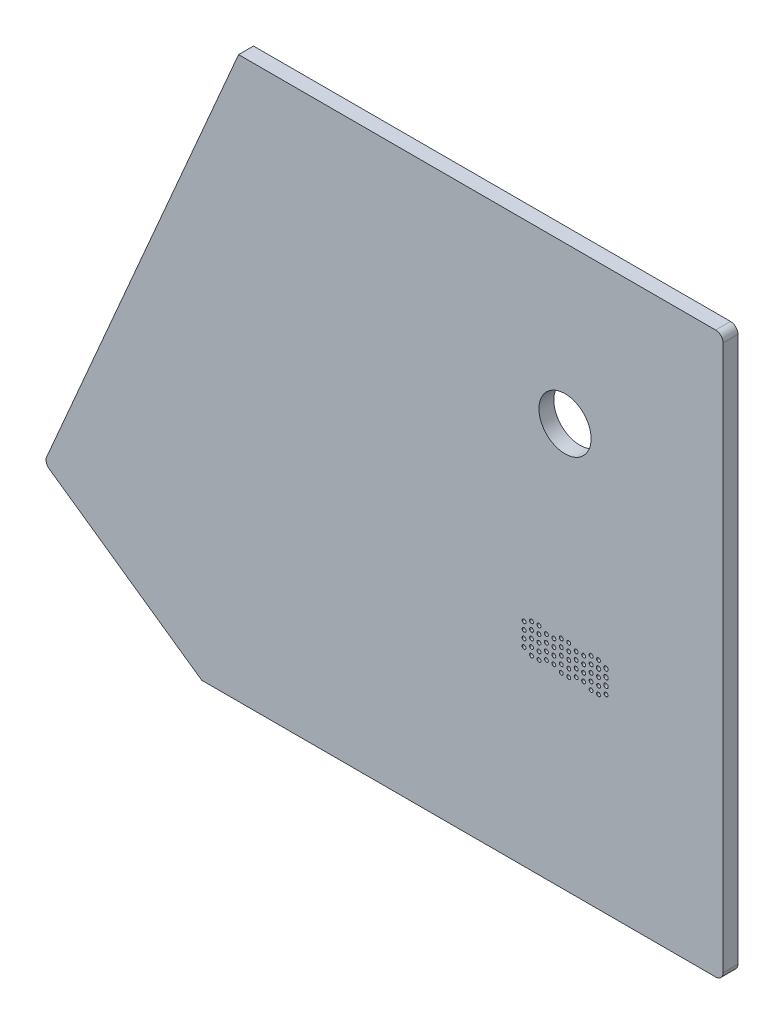
SolidWorks part; units mm, degrees
ref_plane "Plano frontal" through (0, 0, 0) normal (0, 0, 1) x (1, 0, 0)
ref_plane "Plano superior" through (0, 0, 0) normal (0, 1, 0) x (1, 0, 0)
ref_plane "Plano direito" through (0, 0, 0) normal (1, 0, 0) x (0, 0, -1)
sketch "Esboço1" plane through (0, 0, 0) normal (0, 0, 1) x (1, 0, 0)
  line L0 (0, 0) -> (138, 0)
  line L1 (140, 2) -> (140, 148.4543)
  line L2 (138, 150.4543) -> (9.8994, 150.4543)
  line L3 (9.8994, 150.4543) -> (-41.6465, 31.1101)
  line L4 (-40.9576, 28.6788) -> (0, 0)
  line L5 (0, 0) -> (-36.2791, 0) construction
  arc A0 (-41.6465, 31.1101) -> (-40.9576, 28.6788) centre (-39.8104, 30.3171) ccw
  arc A1 (138, 0) -> (140, 2) centre (138, 2) ccw
  arc A2 (140, 148.4543) -> (138, 150.4543) centre (138, 148.4543) ccw
  point P11 (140, 0)
  dimension "D1" = 2
  dimension "D7" = 2
  dimension "D2" = 35
  dimension "D3" = 50
  dimension "D4" = 101.64
  dimension "D5" = 130
  dimension "D6" = 140
extrude "Ressalto-extrusão1" add sketch "Esboço1" along normal blind 4
sketch "Esboço2" plane through (0, 0, 4) normal (0, 0, 1) x (1, 0, 0)
  line L0 (94.5554, 55) -> (94.5554, 53)
  line L1 (0, 0) -> (138, 0) construction
  line L2 (96.5554, 56) -> (98.5554, 56) construction
  line L3 (102.5554, 55) -> (102.5554, 53)
  line L4 (104.5554, 56) -> (106.5554, 56) construction
  line L5 (86.5554, 55) -> (86.5554, 53)
  line L6 (88.5554, 56) -> (90.5554, 56) construction
  line L7 (138, 150.4543) -> (9.8994, 150.4543) construction
  line L8 (140, 2) -> (140, 148.4543) construction
  circle A0 centre (94.5554, 53) radius 0.5
  circle A1 centre (96.5554, 52) radius 0.5
  circle A2 centre (98.5554, 54) radius 0.5
  circle A3 centre (100.5554, 53) radius 0.5
  circle A4 centre (96.5554, 50) radius 0.5
  circle A5 centre (96.5554, 56) radius 0.5
  circle A6 centre (98.5554, 50) radius 0.5
  circle A7 centre (100.5554, 51) radius 0.5
  circle A8 centre (96.5554, 54) radius 0.5
  circle A9 centre (98.5554, 52) radius 0.5
  circle A10 centre (96.5554, 58) radius 0.5
  circle A11 centre (94.5554, 57) radius 0.5
  circle A12 centre (94.5554, 55) radius 0.5
  circle A13 centre (94.5554, 51) radius 0.5
  circle A14 centre (100.5554, 57) radius 0.5
  circle A15 centre (100.5554, 55) radius 0.5
  circle A16 centre (98.5554, 58) radius 0.5
  circle A17 centre (98.5554, 56) radius 0.5
  circle A18 centre (97.5554, 108.4368) radius 7
  circle A19 centre (102.5554, 53) radius 0.5
  circle A20 centre (104.5554, 52) radius 0.5
  circle A21 centre (106.5554, 54) radius 0.5
  circle A22 centre (108.5554, 53) radius 0.5
  circle A23 centre (104.5554, 50) radius 0.5
  circle A24 centre (104.5554, 56) radius 0.5
  circle A25 centre (106.5554, 50) radius 0.5
  circle A26 centre (108.5554, 51) radius 0.5
  circle A27 centre (104.5554, 54) radius 0.5
  circle A28 centre (106.5554, 52) radius 0.5
  circle A29 centre (104.5554, 58) radius 0.5
  circle A30 centre (102.5554, 57) radius 0.5
  circle A31 centre (102.5554, 55) radius 0.5
  circle A32 centre (102.5554, 51) radius 0.5
  circle A33 centre (108.5554, 57) radius 0.5
  circle A34 centre (108.5554, 55) radius 0.5
  circle A35 centre (106.5554, 58) radius 0.5
  circle A36 centre (106.5554, 56) radius 0.5
  circle A37 centre (86.5554, 53) radius 0.5
  circle A38 centre (88.5554, 52) radius 0.5
  circle A39 centre (90.5554, 54) radius 0.5
  circle A40 centre (92.5554, 53) radius 0.5
  circle A41 centre (88.5554, 50) radius 0.5
  circle A42 centre (88.5554, 56) radius 0.5
  circle A43 centre (90.5554, 50) radius 0.5
  circle A44 centre (92.5554, 51) radius 0.5
  circle A45 centre (88.5554, 54) radius 0.5
  circle A46 centre (90.5554, 52) radius 0.5
  circle A47 centre (88.5554, 58) radius 0.5
  circle A48 centre (86.5554, 57) radius 0.5
  circle A49 centre (86.5554, 55) radius 0.5
  circle A50 centre (86.5554, 51) radius 0.5
  circle A51 centre (92.5554, 57) radius 0.5
  circle A52 centre (92.5554, 55) radius 0.5
  circle A53 centre (90.5554, 58) radius 0.5
  circle A54 centre (90.5554, 56) radius 0.5
  point P37 (94.5554, 54)
  point P41 (0, 0)
  point P42 (97.5554, 56)
  point P79 (102.5554, 54)
  point P117 (86.5554, 54)
  point P119 (75.5922, 42.716)
  point P120 (0, 0)
  point P121 (0, 0)
  point P122 (0, 0)
  point P123 (0, 0)
  point P124 (0, 0)
  point P125 (0, 0)
  point P126 (0, 0)
  point P127 (0, 0)
  point P128 (92.5554, 51)
  point P131 (0, 0)
  point P132 (0, 0)
  point P133 (0, 0)
  dimension "D1" = 1
  dimension "D2" = 2
  dimension "D20" = 14
  dimension "D21" = 1
  dimension "D39" = 1
  dimension "D3" = 2
  dimension "D4" = 2
  dimension "D5" = 2
  dimension "D6" = 2
  dimension "D7" = 2
  dimension "D8" = 2
  dimension "D9" = 2
  dimension "D10" = 2
  dimension "D11" = 2
  dimension "D12" = 2
  dimension "D13" = 2
  dimension "D14" = 2
  dimension "D15" = 2
  dimension "D16" = 2
  dimension "D17" = 2
  dimension "D18" = 2
  dimension "D19" = 50
  dimension "D22" = 2
  dimension "D23" = 2
  dimension "D24" = 2
  dimension "D25" = 2
  dimension "D26" = 2
  dimension "D27" = 2
  dimension "D28" = 2
  dimension "D29" = 2
  dimension "D30" = 2
  dimension "D31" = 2
  dimension "D32" = 2
  dimension "D33" = 2
  dimension "D34" = 2
  dimension "D35" = 2
  dimension "D36" = 2
  dimension "D37" = 2
  dimension "D38" = 2
  dimension "D40" = 2
  dimension "D41" = 2
  dimension "D42" = 2
  dimension "D43" = 2
  dimension "D44" = 2
  dimension "D45" = 2
  dimension "D46" = 2
  dimension "D47" = 2
  dimension "D48" = 2
  dimension "D49" = 2
  dimension "D50" = 2
  dimension "D51" = 2
  dimension "D52" = 2
  dimension "D53" = 2
  dimension "D54" = 2
  dimension "D55" = 2
  dimension "D56" = 2
  dimension "D57" = 2
  dimension "D58" = 42.0175
  dimension "D59" = 42.4446
extrude "Corte-extrusão1" cut sketch "Esboço2" against normal through all contours A23
extrude "Corte-extrusão2" cut sketch "Esboço2<7>" against normal through all contours A14
sketch "Esboço2<7>" plane through (0, 0, 4) normal (0, 0, 1) x (1, 0, 0) same geometry as "Esboço2"
extrude "Corte-extrusão3" cut sketch "Esboço2<9>" against normal through all contours A18
sketch "Esboço2<9>" plane through (0, 0, 4) normal (0, 0, 1) x (1, 0, 0) same geometry as "Esboço2"
extrude "Corte-extrusão4" cut sketch "Esboço2<10>" against normal through all contours A47
sketch "Esboço2<10>" plane through (0, 0, 4) normal (0, 0, 1) x (1, 0, 0) same geometry as "Esboço2"
extrude "Corte-extrusão5" cut sketch "Esboço2<11>" against normal through all contours A53
sketch "Esboço2<11>" plane through (0, 0, 4) normal (0, 0, 1) x (1, 0, 0) same geometry as "Esboço2"
hole_wizard "Furo de diâmetro Ø1.15 (1.15)1" positions "3DSketch1" profile "Esboço7" hole size "Ø1.15" standard "AS" end condition through all
sketch3d "3DSketch1"
  point P0 (106.5554, 56, 4)
  point P3 (108.5554, 57, 4)
  point P6 (108.5554, 55, 4)
  point P9 (108.5554, 53, 4)
sketch "Esboço7" plane through (106.5554, 56, 4) normal (1, 0, 0) x (0, -1, 0)
  line L0 (0, 0) -> (0, 4)
  line L1 (0, 4) -> (0.575, 4)
  line L2 (0.575, 4) -> (0.575, 0.025)
  line L3 (0.575, 0.025) -> (0.6, 0)
  line L5 (0.6, 0) -> (0, 0)
  line L6 (-0.575, 0.025) -> (-0.6, 0) construction
  line L11 (0, -6.35) -> (0, 107.95) construction
  dimension "Thru Hole Dia." = 1.15
  dimension "Thru Hole Depth" = 4
  dimension "Near C'Sink Dia." = 1.2
  dimension "Near C'Sink Angle" = 90
hole_wizard "Furo de diâmetro Ø1.0 (1)1" positions "3DSketch2" profile "Esboço8" hole size "Ø1.0" standard "AS" end condition through all
sketch3d "3DSketch2"
  point P0 (106.5554, 58, 4)
  point P3 (104.5554, 58, 4)
  point P6 (102.5554, 57, 4)
  point P9 (100.5554, 57, 4)
  point P12 (102.5554, 55, 4)
  point P15 (104.5554, 56, 4)
  point P18 (104.5554, 54, 4)
  point P21 (106.5554, 54, 4)
  point P24 (106.5554, 52, 4)
  point P27 (108.5554, 51, 4)
  point P30 (106.5554, 50, 4)
  point P33 (104.5554, 52, 4)
  point P36 (92.5554, 57, 4)
  point P39 (92.5554, 55, 4)
  point P42 (92.5554, 53, 4)
  point P45 (92.5554, 51, 4)
  point P48 (94.5554, 51, 4)
  point P51 (96.5554, 50, 4)
  point P54 (98.5554, 50, 4)
  point P57 (100.5554, 51, 4)
  point P60 (102.5554, 51, 4)
  point P63 (102.5554, 53, 4)
  point P66 (100.5554, 53, 4)
  point P69 (100.5554, 55, 4)
  point P72 (98.5554, 56, 4)
  point P75 (98.5554, 58, 4)
  point P78 (96.5554, 58, 4)
  point P81 (96.5554, 56, 4)
  point P84 (96.5554, 54, 4)
  point P87 (98.5554, 54, 4)
  point P90 (96.5554, 52, 4)
  point P93 (98.5554, 52, 4)
  point P96 (94.5554, 53, 4)
  point P99 (94.5554, 55, 4)
  point P102 (94.5554, 57, 4)
  point P105 (88.5554, 58, 4)
  point P108 (90.5554, 58, 4)
  point P111 (86.5554, 57, 4)
  point P114 (88.5554, 56, 4)
  point P117 (90.5554, 56, 4)
  point P120 (90.5554, 54, 4)
  point P123 (90.5554, 52, 4)
  point P126 (90.5554, 50, 4)
  point P129 (88.5554, 50, 4)
  point P132 (88.5554, 52, 4)
  point P135 (88.5554, 54, 4)
  point P138 (86.5554, 55, 4)
  point P141 (86.5554, 53, 4)
  point P144 (86.5554, 51, 4)
sketch "Esboço8" plane through (106.5554, 58, 4) normal (1, 0, 0) x (0, -1, 0)
  line L0 (0, 0) -> (0, 4)
  line L1 (0, 4) -> (0.5, 4)
  line L2 (0.5, 4) -> (0.5, 0.025)
  line L3 (0.5, 0.025) -> (0.525, 0)
  line L5 (0.525, 0) -> (0, 0)
  line L6 (-0.5, 0.025) -> (-0.525, 0) construction
  line L11 (0, -6.35) -> (0, 107.95) construction
  dimension "Thru Hole Dia." = 1
  dimension "Thru Hole Depth" = 4
  dimension "Near C'Sink Dia." = 1.05
  dimension "Near C'Sink Angle" = 90
